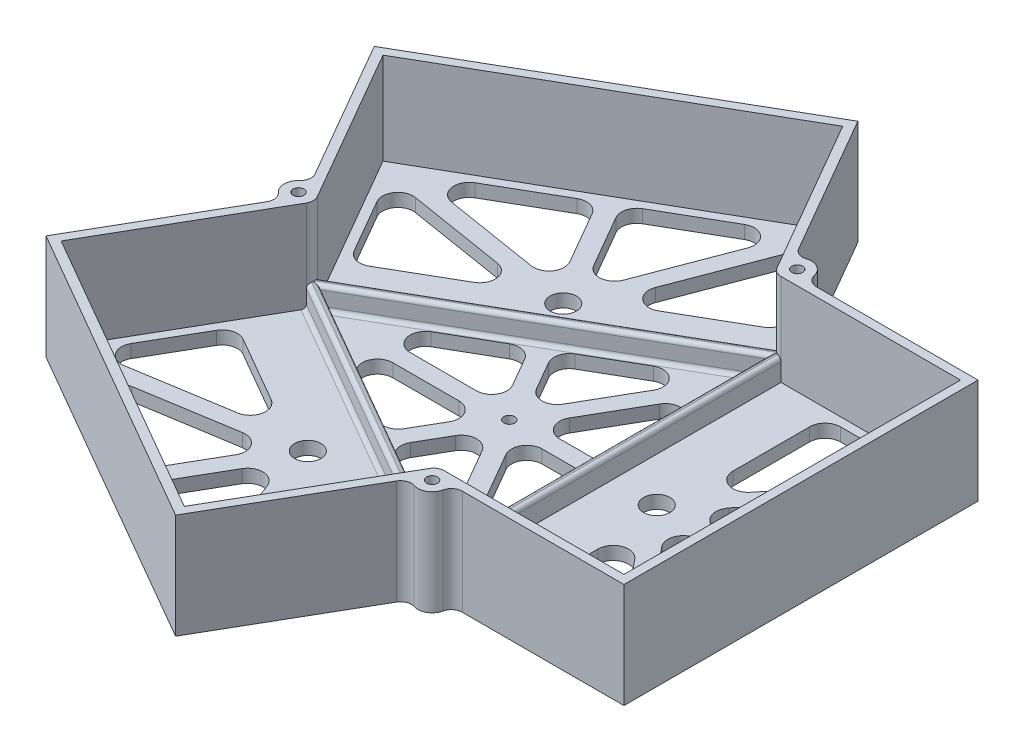
SolidWorks part; units mm, degrees
ref_plane "Front Plane" through (0, 0, 0) normal (0, 0, 1) x (1, 0, 0)
ref_plane "Top Plane" through (0, 0, 0) normal (0, 1, 0) x (1, 0, 0)
ref_plane "Right Plane" through (0, 0, 0) normal (1, 0, 0) x (0, 0, -1)
sketch "Sketch1" plane through (0, 0, 0) normal (0, 1, 0) x (1, 0, 0)
  line L0 (19.5158, -90.1492) -> (5.5625, -53.4677)
  line L5 (23.4295, -18.521) -> (22.1795, -20.6861)
  line L6 (85.5432, -56.1036) -> (56.6565, -56.1036) construction
  line L7 (89.5432, -60.1036) -> (89.5432, 20.8964)
  line L8 (-10.5648, -77.401) -> (24.5092, -97.651)
  line L9 (-27.1955, -27.3848) -> (-27.1955, -21.6036)
  line L10 (-10.5648, -77.401) -> (-45.6389, -57.151)
  line L11 (-45.6389, -57.151) -> (-29.1955, -28.6702)
  line L12 (-45.6389, 17.9439) -> (-29.1955, -10.5369)
  line L13 (24.5092, 58.4439) -> (40.9526, 29.9631)
  line L14 (-27.1955, -19.6036) -> (20.4951, -19.6036)
  line L19 (-45.6389, 17.9439) -> (24.5092, 58.4439)
  line L20 (89.5432, 20.8964) -> (56.6565, 20.8964)
  line L21 (89.5432, -60.1036) -> (56.6565, -60.1036)
  line L22 (24.5092, -97.651) -> (40.9526, -69.1702)
  line L23 (41.0658, 27.5883) -> (46.0725, 24.6977)
  line L24 (5.2031, -46.0901) -> (-27.1955, -27.3848)
  line L25 (47.8045, 23.6977) -> (23.9592, -17.6036)
  line L26 (-29.1955, -28.6702) -> (-29.1955, -10.5369)
  line L27 (0.0674, -47.7438) -> (-26.6748, -32.3042)
  line L28 (58.5432, -25.2243) -> (58.5432, -56.1036)
  line L29 (40.9526, -69.1702) -> (56.6565, -60.1036)
  line L34 (40.9526, 29.9631) -> (56.6565, 20.8964)
  line L35 (54.5432, -21.6036) -> (54.5432, -59.0142)
  line L36 (9.8029, 14.1574) -> (36.5451, 29.5971)
  line L37 (49.5366, 22.6977) -> (54.5432, 19.8071)
  line L38 (54.5432, -59.0142) -> (49.5366, -61.9048)
  line L39 (8.6672, 8.883) -> (41.0658, 27.5883)
  line L40 (47.8045, -62.9048) -> (23.9592, -21.6036)
  line L41 (21.6498, -17.6036) -> (7.2251, 7.3808)
  line L42 (21.5545, -19.6036) -> (24.0545, -19.6036)
  line L43 (21.6498, -21.6036) -> (7.2251, -46.5879)
  line L44 (23.4295, -20.6861) -> (22.1795, -18.521)
  line L45 (-26.6748, -6.9029) -> (0.0674, 8.5367)
  line L46 (58.5432, 16.8964) -> (58.5432, -13.9828)
  line L47 (36.5451, -68.8042) -> (9.8029, -53.3646)
  line L48 (-27.1955, -11.8224) -> (5.2031, 6.883)
  line L49 (54.5432, 19.8071) -> (54.5432, -17.6036)
  line L50 (41.0658, -66.7954) -> (8.6672, -48.0901)
  line L51 (46.0725, 24.6977) -> (22.8045, -15.6036)
  line L52 (-27.1955, -21.6036) -> (19.3404, -21.6036)
  line L53 (49.5366, -61.9048) -> (26.2686, -21.6036)
  line L54 (49.5366, 22.6977) -> (26.2686, -17.6036)
  line L55 (-27.1955, -17.6036) -> (19.3404, -17.6036)
  line L56 (46.0725, -63.9048) -> (22.8045, -23.6036)
  line L57 (25.1139, -19.6036) -> (53.9634, -19.6036)
  line L59 (22.8045, -15.6036) -> (8.6672, 8.883)
  line L60 (26.2686, -17.6036) -> (54.5432, -17.6036)
  line L61 (19.3404, -21.6036) -> (5.2031, -46.0901)
  line L62 (19.3404, -17.6036) -> (5.2031, 6.883)
  line L63 (26.2686, -21.6036) -> (54.5432, -21.6036)
  line L64 (22.8045, -23.6036) -> (8.6672, -48.0901)
  line L71 (-14.9083, -21.6036) -> (10.7782, -36.4337)
  line L73 (43.393, -51.2638) -> (43.393, -21.6036)
  line L75 (39.9289, 14.0567) -> (14.2423, -0.7734)
  line L76 (43.393, -17.6036) -> (43.393, 12.0567)
  line L77 (-39.2552, 14.887) -> (-26.6748, -6.9029)
  line L78 (-36.6455, 18.5174) -> (-10.2969, 33.7297)
  line L79 (23.9646, 51.387) -> (36.5451, 29.5971)
  line L80 (23.9646, -90.5942) -> (36.5451, -68.8042)
  line L81 (-6.8328, -74.9369) -> (19.5158, -90.1492)
  line L82 (-10.2969, -72.9369) -> (-36.6455, -57.7245)
  line L83 (-39.2552, -54.0942) -> (-26.6748, -32.3042)
  line L84 (83.7041, 16.8964) -> (58.5432, 16.8964)
  line L85 (10.7782, -2.7734) -> (-14.9083, -17.6036)
  line L86 (85.5432, -52.0283) -> (85.5432, -21.6036)
  line L87 (83.7041, -56.1036) -> (58.5432, -56.1036)
  line L88 (-8.5648, -73.9369) -> (-40.1748, -55.6869) construction
  line L89 (14.2423, -38.4337) -> (39.9289, -53.2638)
  line L90 (0.0674, -47.7438) -> (-39.2552, -54.0942)
  line L91 (-40.1748, -55.6869) -> (-25.7314, -30.6702) construction
  line L92 (23.0451, -92.1869) -> (37.4885, -67.1702) construction
  line L93 (-8.5648, -73.9369) -> (23.0451, -92.1869) construction
  line L94 (23.9646, -90.5942) -> (9.8029, -53.3646)
  line L95 (-27.1955, -17.6036) -> (-27.1955, -11.8224)
  line L96 (-40.1748, 16.4797) -> (-25.7314, -8.5369) construction
  line L97 (83.7041, 16.8964) -> (58.5432, -13.9828)
  line L98 (46.0725, -63.9048) -> (41.0658, -66.7954)
  line L99 (-40.1748, 16.4797) -> (23.0451, 52.9797) construction
  line L100 (9.8029, 14.1574) -> (23.9646, 51.387)
  line L101 (-39.2552, 14.887) -> (0.0674, 8.5367)
  line L102 (2.0984, -51.4677) -> (-36.6455, -57.7245)
  line L103 (85.5432, 12.8211) -> (60.7527, -17.6036)
  line L104 (60.7527, -21.6036) -> (85.5432, -52.0283)
  line L105 (85.5432, 16.8964) -> (56.6565, 16.8964) construction
  line L106 (5.5625, 14.2605) -> (19.5158, 50.9421)
  line L107 (-36.6455, 18.5174) -> (2.0984, 12.2605)
  line L108 (23.0451, 52.9797) -> (37.4885, 27.9631) construction
  line L109 (85.5432, -56.1036) -> (85.5432, 16.8964) construction
  line L110 (85.5432, -17.6036) -> (85.5432, 12.8211)
  line L111 (58.5432, -25.2243) -> (83.7041, -56.1036)
  line L112 (-6.8328, 35.7297) -> (19.5158, 50.9421)
  line L114 (85.5432, -17.6036) -> (60.7527, -17.6036)
  line L115 (5.5625, 14.2605) -> (-6.8328, 35.7297)
  line L116 (-6.8328, -74.9369) -> (5.5625, -53.4677)
  line L117 (85.5432, -21.6036) -> (60.7527, -21.6036)
  line L118 (2.0984, 12.2605) -> (-10.2969, 33.7297)
  line L119 (-10.2969, -72.9369) -> (2.0984, -51.4677)
  circle A12 centre (5.9352, -48.8222) radius 3
  circle A13 centre (5.9352, 9.615) radius 3
  circle A14 centre (56.5432, -19.6036) radius 3
  circle A15 centre (22.8045, -19.6036) radius 1.25
  point P6 (89.5432, -19.6036)
  point P11 (-10.5648, -77.401)
  point P14 (-10.5648, 38.1939)
  point P15 (-10.5648, -77.401)
  point P26 (-29.1955, -19.6036)
  point P32 (48.8045, -64.6369)
  point P36 (48.8045, 25.4297)
  point P69 (22.8045, -19.6036)
  point P103 (22.8045, -19.6036)
  dimension "D7" = 6
  dimension "D1" = 4
  dimension "D5" = 6
  dimension "D6" = 6
  dimension "D2" = 28.8495
  dimension "D3" = 28.8495
  dimension "D4" = 28.8495
extrude "Boss-Extrude1" add sketch "Sketch1" along normal blind 3 contours L34 L13 L19 L12 L26 L11 L10 L8 L22 L29 L21 L7 L20 A15 A14 A13 A12 L107 L78 L106 L104 L103 | L76 L60 L49 L37 L54 | L75 L51 L23 L39 L59 | L95 L55 L85 L62 L48 | L71 L52 L9 L24 L61 | L98 L56 L89 L64 L50 | L73 L53 L38 L35 L63 region at (73.0998, 0, 58.0386) region at (-8.1259, 0, 32.202) region at (27.3592, 0, 52.6893) region at (27.3592, 0, -13.4822) region at (-8.1259, 0, 7.0052) region at (49.1803, 0, 40.0909) region at (49.1803, 0, -0.8838)
sketch "Sketch2" plane through (0, 3, 0) normal (0, 1, 0) x (1, 0, 0)
  line L0 (-21.6515, -19.6036) -> (-42.9068, 17.2118)
  line L1 (-45.6389, 17.9439) -> (24.5092, 58.4439)
  line L2 (24.5092, 58.4439) -> (40.9526, 29.9631)
  line L3 (40.9526, 29.9631) -> (56.6565, 20.8964)
  line L4 (56.6565, 20.8964) -> (89.5432, 20.8964)
  line L5 (89.5432, 20.8964) -> (89.5432, -60.1036)
  line L6 (89.5432, -60.1036) -> (56.6565, -60.1036)
  line L7 (56.6565, -60.1036) -> (40.9526, -69.1702)
  line L8 (40.9526, -69.1702) -> (24.5092, -97.651)
  line L9 (24.5092, -97.651) -> (-45.6389, -57.151)
  line L10 (-45.6389, -57.151) -> (-29.1955, -28.6702)
  line L11 (-29.1955, -28.6702) -> (-29.1955, -10.5369)
  line L12 (-29.1955, -10.5369) -> (-45.6389, 17.9439)
  line L13 (-42.9068, 17.2118) -> (23.7771, 55.7118)
  line L14 (23.7771, 55.7118) -> (45.0325, 18.8964)
  line L16 (45.0325, 18.8964) -> (87.5432, 18.8964)
  line L17 (87.5432, 18.8964) -> (87.5432, -58.1036)
  line L18 (87.5432, -58.1036) -> (45.0325, -58.1036)
  line L20 (45.0325, -58.1036) -> (23.7771, -94.9189)
  line L21 (23.7771, -94.9189) -> (-42.9068, -56.4189)
  line L22 (-42.9068, -56.4189) -> (-21.6515, -19.6036)
  line L24 (-42.9068, -56.4189) -> (-27.1955, -29.2061) construction
  line L25 (-27.1955, -10.001) -> (-42.9068, 17.2118) construction
  line L26 (23.7771, 55.7118) -> (39.4885, 28.499) construction
  line L27 (56.1206, 18.8964) -> (87.5432, 18.8964) construction
  line L28 (87.5432, -58.1036) -> (56.1206, -58.1036) construction
  line L29 (39.4885, -67.7061) -> (23.7771, -94.9189) construction
  line L30 (-27.1955, -29.2061) -> (-27.1955, -10.001) construction
  line L31 (39.4885, 28.499) -> (56.1206, 18.8964) construction
  line L32 (56.1206, -58.1036) -> (39.4885, -67.7061) construction
  line L33 (-21.6515, -19.6036) -> (-29.1955, -19.6036)
  line L34 (45.0325, 18.8964) -> (48.8045, 25.4297)
  line L35 (45.0325, -58.1036) -> (48.8045, -64.6369)
  circle A0 centre (-25.4235, -19.6036) radius 1.25
  circle A2 centre (46.9185, 22.1631) radius 1.25
  circle A3 centre (46.9185, -61.3702) radius 1.25
  dimension "D1" = 2
extrude "Boss-Extrude2" add sketch "Sketch2" along normal blind 21 contours A2 L34 L3 L33 A0 L0 L13 L14 | A3 L35 L20 L21 L22 L33 A0 L11 | A3 L35 L7 L34 A2 L16 L17 L18 region at (-22.9125, 3, 18.3784) region at (-33.3402, 3, 37.3987) region at (46.5331, 3, -19.4862)
sketch "Sketch4" plane through (0, 24, 0) normal (0, 1, 0) x (1, 0, 0)
  line L0 (-29.1955, -10.5369) -> (-25.8321, -16.3626)
  line L1 (-29.1955, -28.6702) -> (-25.8321, -22.8446)
  line L2 (-29.1955, -28.6702) -> (-29.1955, -10.5369)
  line L3 (40.9526, 29.9631) -> (56.6565, 20.8964)
  line L4 (56.6565, 20.8964) -> (49.9296, 20.8964)
  line L5 (40.9526, 29.9631) -> (44.316, 24.1374)
  line L6 (56.6565, -60.1036) -> (40.9526, -69.1702)
  line L7 (40.9526, -69.1702) -> (44.316, -63.3446)
  line L8 (56.6565, -60.1036) -> (49.9296, -60.1036)
  arc A0 (-25.8321, -16.3626) -> (-25.8321, -22.8446) centre (-25.4235, -19.6036) ccw
  arc A1 (49.9296, 20.8964) -> (44.316, 24.1374) centre (46.9185, 22.1631) ccw
  arc A2 (44.316, -63.3446) -> (49.9296, -60.1036) centre (46.9185, -61.3702) ccw
  point P21 (22.8045, -19.6036)
  dimension "D1" = 3
extrude "Cut-Extrude1" cut sketch "Sketch4" against normal through all
fillet "Fillet1" radius 2.5 9 edges at (45.0325, 13.5, -18.8964) (44.316, 12, -24.1374) (49.9296, 12, -20.8964) (44.316, 12, 63.3446) (49.9296, 12, 60.1036) (45.0325, 13.5, 58.1036) (-21.6515, 13.5, 19.6036) (-25.8321, 12, 22.8446) (-25.8321, 12, 16.3626)
sketch "Sketch5" plane through (0, 3, 0) normal (0, 1, 0) x (1, 0, 0)
  line L0 (-22.3731, -20.8536) -> (44.3108, -59.3536)
  line L1 (46.4759, -58.1036) -> (46.4759, 18.8964)
  line L2 (44.3108, 20.1464) -> (-22.3731, -18.3536)
  line L3 (44.4759, 17.9323) -> (-20.5382, -19.6036)
  line L4 (-20.5382, -19.6036) -> (44.4759, -57.1395)
  line L5 (44.4759, -57.1395) -> (44.4759, 17.9323)
  line L6 (45.3108, 18.4144) -> (-21.3731, -20.0856) construction
  line L7 (-21.3731, -19.1215) -> (45.3108, -57.6215) construction
  line L8 (44.4759, -58.1036) -> (44.4759, 18.8964) construction
  arc A0 (-22.3731, -20.8536) -> (-22.3731, -18.3536) centre (-24.5382, -19.6036) ccw
  arc A1 (44.3108, 20.1464) -> (46.4759, 18.8964) centre (46.4759, 21.3964) ccw
  arc A2 (46.4759, -58.1036) -> (44.3108, -59.3536) centre (46.4759, -60.6036) ccw
  dimension "D1" = 2
extrude "Boss-Extrude3" add sketch "Sketch5" along normal blind 5
fillet "Fillet2" radius 0.9 9 edges at (11.9688, 8, 38.3715) (10.9688, 8, 40.1036) (10.9688, 3, 40.1036) (46.4759, 8, 19.6036) (44.4759, 8, 19.6036) (44.4759, 3, 19.6036) (10.9688, 8, -0.8964) (11.9688, 8, 0.8356) (11.9688, 3, 0.8356)
fillet "Fillet3" radius 3.5 54 edges at (14.2423, 1.5, 38.4337) (43.393, 1.5, 51.2638) (39.9289, 1.5, 53.2638) (-14.9083, 1.5, 21.6036) (10.7782, 1.5, 36.4337) (43.393, 1.5, 21.6036) (43.393, 1.5, 17.6036) (26.2686, 1.5, 17.6036) (26.2686, 1.5, 21.6036) (22.8045, 1.5, 23.6036) (19.3404, 1.5, 21.6036) (22.8045, 1.5, 15.6036) (14.2423, 1.5, 0.7734) (43.393, 1.5, -12.0567) (39.9289, 1.5, -14.0567) (19.3404, 1.5, 17.6036) (-14.9083, 1.5, 17.6036) (10.7782, 1.5, 2.7734) (58.5432, 1.5, -16.8964) (83.7041, 1.5, -16.8964) (85.5432, 1.5, -12.8211) (83.7041, 1.5, 56.1036) (85.5432, 1.5, 52.0283) (85.5432, 1.5, 17.6036) (85.5432, 1.5, 21.6036) (58.5432, 1.5, 25.2243) (60.7527, 1.5, 21.6036) (60.7527, 1.5, 17.6036) (58.5432, 1.5, 13.9828) (58.5432, 1.5, 56.1036) (23.9646, 1.5, 90.5942) (36.5451, 1.5, 68.8042) (19.5158, 1.5, 90.1492) (-6.8328, 1.5, 74.9369) (-10.2969, 1.5, 72.9369) (-36.6455, 1.5, 57.7245) (-39.2552, 1.5, 54.0942) (-26.6748, 1.5, 32.3042) (9.8029, 1.5, 53.3646) (5.5625, 1.5, 53.4677) (2.0984, 1.5, 51.4677) (0.0674, 1.5, 47.7438) (23.9646, 1.5, -51.387) (36.5451, 1.5, -29.5971) (9.8029, 1.5, -14.1574) (5.5625, 1.5, -14.2605) (2.0984, 1.5, -12.2605) (0.0674, 1.5, -8.5367) (19.5158, 1.5, -50.9421) (-6.8328, 1.5, -35.7297) (-10.2969, 1.5, -33.7297) (-26.6748, 1.5, 6.9029) (-36.6455, 1.5, -18.5174) (-39.2552, 1.5, -14.887)
